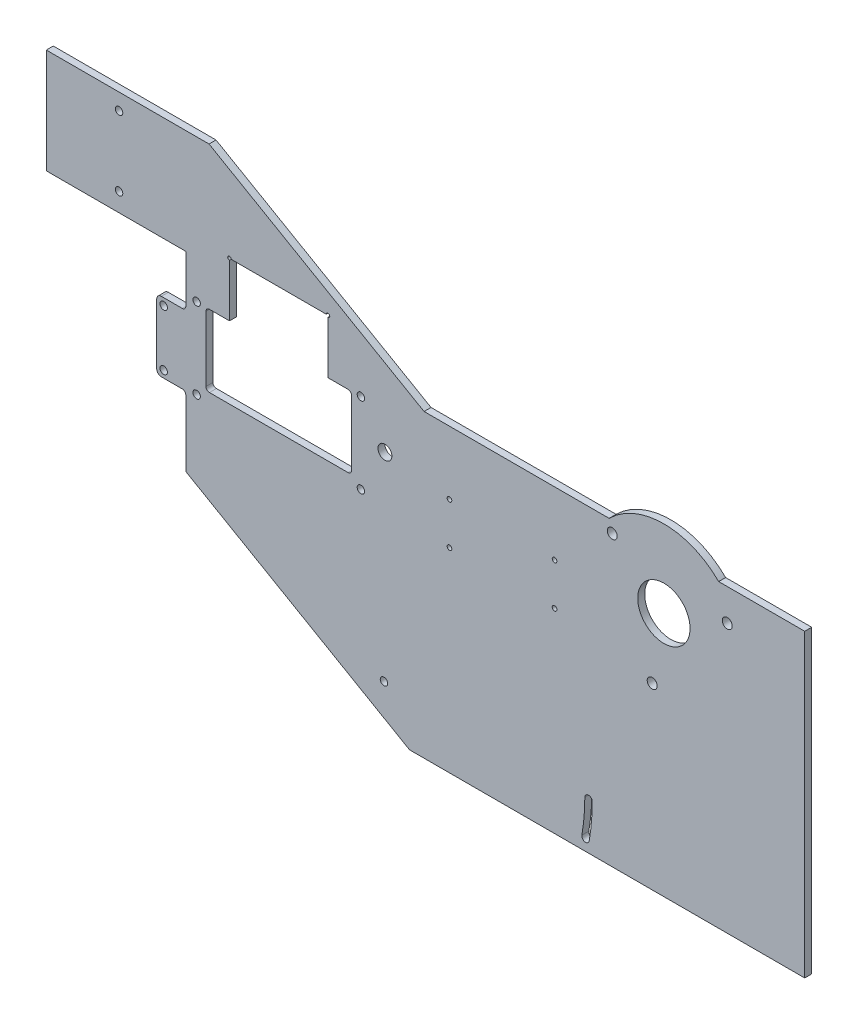
SolidWorks part; units mm, degrees
material "Thornel Mat VMA"
ref_plane "Front Plane" through (0, 0, 0) normal (0, 0, 1) x (1, 0, 0)
ref_plane "Top Plane" through (0, 0, 0) normal (0, 1, 0) x (1, 0, 0)
ref_plane "Right Plane" through (0, 0, 0) normal (1, 0, 0) x (0, 0, -1)
sketch "Sketch1" plane through (0, 0, 0) normal (0, 0, 1) x (1, 0, 0)
  line L1 (20.2869, 47.6) -> (204.7012, 47.6)
  line L2 (20.2869, 47.6) -> (20.2869, -36.0143)
  line L3 (20.2869, -36.0143) -> (204.7012, -36.0143)
  line L4 (204.7012, 47.6) -> (204.7012, -36.0143)
extrude "Boss-Extrude1" add sketch "Sketch1" along normal blind 3
sketch "Sketch2" plane through (0, 0, 0) normal (0, 0, -1) x (-1, 0, 0)
  circle A0 centre (-24.1169, 24) radius 3
  dimension "D1" = 6
extrude "Cut-Extrude1" cut sketch "Sketch2" against normal blind 70
sketch "Sketch3" plane through (0, 0, 3) normal (0, 0, 1) x (1, 0, 0)
  line L0 (24.1169, 24) -> (144.1169, 24) construction
  circle A0 centre (144.1169, 24) radius 11.25
  dimension "D2" = 22.5
  dimension "D1" = 120
extrude "Cut-Extrude2" cut sketch "Sketch3" against normal blind 3
sketch "Sketch4" plane through (0, 0, 3) normal (0, 0, 1) x (1, 0, 0)
  line L0 (-61.5431, 47.6) -> (-61.5431, -3) construction
  line L1 (-61.5431, 56) -> (-61.5431, 34)
  line L2 (-61.5431, 4) -> (-61.5431, -26)
  line L3 (-61.5431, 34) -> (-72.0431, 34)
  line L5 (-61.5431, 4) -> (-72.0431, 4)
  line L6 (-74.0431, 32) -> (-74.0431, 6)
  line L7 (-51.5431, 101) -> (-121.5431, 101)
  line L8 (-121.5431, 101) -> (-121.5431, 56)
  line L9 (-121.5431, 56) -> (-61.5431, 56)
  line L10 (-51.5431, 101) -> (40.9484, 47.6)
  line L11 (20.2869, 47.6) -> (20.2869, -36.0143)
  line L12 (20.2869, -36.0143) -> (204.7012, -36.0143)
  line L13 (204.7012, -36.0143) -> (204.7012, 47.6)
  line L14 (204.7012, 47.6) -> (20.2869, 47.6)
  line L15 (20.2869, 47.6) -> (20.2869, -36.0143)
  line L16 (20.2869, -36.0143) -> (204.7012, -36.0143)
  line L18 (40.9484, 47.6) -> (20.2869, 47.6)
  line L19 (-61.5431, -26) -> (34.7012, -81.5667)
  line L20 (34.7012, -81.5667) -> (204.7012, -81.5667)
  line L21 (204.7012, -81.5667) -> (204.7012, -36.0143)
  line L22 (-85.0431, 56) -> (-64.7431, 56) construction
  circle A0 centre (-71.0431, 31) radius 1.6
  circle A1 centre (-71.0431, 7) radius 1.6
  arc A2 (-72.0431, 4) -> (-74.0431, 6) centre (-72.0431, 6) cw
  arc A3 (-72.0431, 34) -> (-74.0431, 32) centre (-72.0431, 32) ccw
  point P30 (-10.4119, -51.6927)
  dimension "D1" = 3.2
  dimension "D2" = 3
  dimension "D5" = 2
  dimension "D3" = 3
  dimension "D4" = 3
  dimension "D7" = 60
  dimension "D8" = 45
  dimension "D9" = 30
  dimension "D10" = 30
  dimension "D11" = 70
  dimension "D12" = 170
  dimension "D6" = 0
extrude "Boss-Extrude2" add sketch "Sketch4" against normal blind 3
sketch "Sketch5" plane through (0, 0, 3) normal (0, 0, 1) x (1, 0, 0)
  line L0 (-0.5431, 62.6) -> (-42.5431, 62.6) construction
  line L1 (8.2869, 8.5) -> (-51.3731, 8.5)
  line L2 (9.7869, 10) -> (9.7869, 38)
  line L3 (8.2869, 39.5) -> (-0.3431, 39.5)
  line L4 (-52.8731, 10) -> (-52.8731, 38)
  line L5 (-41.9931, 62.8) -> (-1.0931, 62.8)
  line L6 (-42.7431, 62.05) -> (-42.7431, 39.5)
  line L8 (-0.3431, 62.05) -> (-0.3431, 39.5)
  line L9 (-42.5431, 57.6) -> (-42.5431, 52.6) construction
  line L10 (-0.5431, 62.6) -> (-0.5431, 57.6) construction
  line L11 (-42.7431, 39.5) -> (-51.3731, 39.5)
  line L13 (7.7869, 47.6) -> (7.7869, -3) construction
  line L14 (-50.8731, -3) -> (-50.8731, 47.6) construction
  line L15 (8.4569, 34.5) -> (-51.5431, 34.5) construction
  line L16 (-51.5431, 13.5) -> (8.4569, 13.5) construction
  arc A0 (9.7869, 38) -> (8.2869, 39.5) centre (8.2869, 38) ccw
  arc A1 (8.2869, 8.5) -> (9.7869, 10) centre (8.2869, 10) ccw
  arc A2 (-51.3731, 8.5) -> (-52.8731, 10) centre (-51.3731, 10) cw
  arc A3 (-51.3731, 39.5) -> (-52.8731, 38) centre (-51.3731, 38) ccw
  arc A4 (-41.9931, 62.8) -> (-42.7431, 62.05) centre (-42.7431, 62.8) ccw
  arc A6 (-1.0931, 62.8) -> (-0.3431, 62.05) centre (-0.3431, 62.8) cw
  point P34 (0, 0)
  point P35 (-0.3431, 62.365)
  point P36 (0, 0)
  point P37 (-42.9098, 62.9019)
  point P38 (0, 0)
  dimension "D8" = 1.5
  dimension "D9" = 1.5
  dimension "D10" = 0.75
  dimension "D1" = 0.2
  dimension "D2" = 0.2
  dimension "D3" = 0.2
  dimension "D4" = 2
  dimension "D5" = 2
  dimension "D6" = 5
  dimension "D7" = 5
extrude "Cut-Extrude3" cut sketch "Sketch5" against normal blind 10 contours L8 L5 L6 L3 | L4 L1 L2 L3 region at (-21.5431, 33.186, 3)
sketch "Sketch6" plane through (0, 0, 3) normal (0, 0, 1) x (1, 0, 0)
  line L0 (-61.5431, -3) -> (-50.8731, -3) construction
  line L1 (13.7869, 5) -> (-56.8731, 5) construction
  line L2 (13.7869, 5) -> (13.7869, 39.6) construction
  line L3 (13.7869, 39.6) -> (-56.8731, 39.6) construction
  line L4 (-56.8731, 5) -> (-56.8731, 39.6) construction
  line L5 (-61.5431, 47.6) -> (-50.8731, 47.6) construction
  line L6 (-52.8731, 10) -> (-52.8731, 38) construction
  line L7 (9.7869, 10) -> (9.7869, 38) construction
  circle A0 centre (13.7869, 5) radius 1.6
  circle A1 centre (13.7869, 39.6) radius 1.6
  circle A2 centre (-56.8731, 5) radius 1.6
  circle A3 centre (-56.8731, 39.6) radius 1.6
  dimension "D5" = 3.2
  dimension "D1" = 8
  dimension "D2" = 8
  dimension "D3" = 4
  dimension "D4" = 4
extrude "Cut-Extrude4" cut sketch "Sketch6" against normal blind 3
fillet "Fillet1" radius 1.5 2 edges at (-61.5431, 4, 1.5) (-61.5431, 34, 1.5)
sketch "Sketch7" plane through (0, 0, 3) normal (0, 0, 1) x (1, 0, 0)
  arc A0 (51.8869, 1.3333) -> (51.8869, 3.3333) centre (51.8869, 2.3333) ccw construction
  arc A1 (97.0869, 1.3333) -> (97.0869, 3.3333) centre (97.0869, 2.3333) ccw construction
  arc A2 (97.0869, 19.3333) -> (97.0869, 21.3333) centre (97.0869, 20.3333) ccw construction
  arc A3 (51.8869, 19.3333) -> (51.8869, 21.3333) centre (51.8869, 20.3333) ccw construction
  circle A4 centre (51.8869, 2.3333) radius 1
  circle A5 centre (97.0869, 2.3333) radius 1
  circle A6 centre (97.0869, 20.3333) radius 1
  circle A7 centre (51.8869, 20.3333) radius 1
  point P12 (51.2974, 30.8803)
  point P14 (96.5783, 30.8803)
  point P16 (51.4071, 12.8803)
  point P18 (96.5458, 12.8803)
extrude "Cut-Extrude5" cut sketch "Sketch7" against normal blind 10
sketch "Sketch8" plane through (0, 0, 3) normal (0, 0, 1) x (1, 0, 0)
  circle A0 centre (-90.2431, 94) radius 1.6
  circle A1 centre (-90.2431, 64) radius 1.6
  dimension "D1" = 3.2
extrude "Cut-Extrude6" cut sketch "Sketch8" against normal blind 12
sketch "Sketch9" plane through (0, 0, 0) normal (0, 0, -1) x (-1, 0, 0)
  circle A0 centre (-171.368, 33.9186) radius 2.15
  circle A1 centre (-121.9016, 42.6408) radius 2.15
  circle A2 centre (-139.0811, -4.5594) radius 2.15
  dimension "D1" = 4.3
extrude "Cut-Extrude7" cut sketch "Sketch9" against normal blind 12
sketch "Sketch10" plane through (0, 0, 0) normal (0, 0, -1) x (-1, 0, 0)
  line L0 (-204.7012, 47.6) -> (-40.9484, 47.6) construction
  line L1 (-167.6809, 47.6) -> (-120.5529, 47.6)
  arc A0 (-120.5529, 47.6) -> (-167.6809, 47.6) centre (-144.1169, 24) ccw
  dimension "D1" = 66.7
extrude "Boss-Extrude3" add sketch "Sketch10" against normal blind 3
sketch "Sketch12" plane through (0, 0, 3) normal (0, 0, 1) x (1, 0, 0)
  line L0 (34.7012, -81.5667) -> (204.7012, -81.5667) construction
  circle A0 centre (23.7012, -61.5667) radius 1.6
  arc A1 (111.7012, -61.5667) -> (110.4134, -76.5667) centre (23.7012, -61.5667) cw construction
  arc A2 (110.1012, -61.5667) -> (108.8368, -76.294) centre (23.7012, -61.5667) cw
  arc A3 (113.3012, -61.5667) -> (111.99, -76.8394) centre (23.7012, -61.5667) cw
  arc A4 (113.3012, -61.5667) -> (110.1012, -61.5667) centre (111.7012, -61.5667) ccw
  arc A5 (111.99, -76.8394) -> (108.8368, -76.294) centre (110.4134, -76.5667) cw
  point P3 (0, 0)
  point P14 (110.1012, -77.1186)
  point P15 (0, 0)
  dimension "D1" = 3.2
  dimension "D2" = 1.6
  dimension "D3" = 5
extrude "Cut-Extrude8" cut sketch "Sketch12" against normal blind 10
